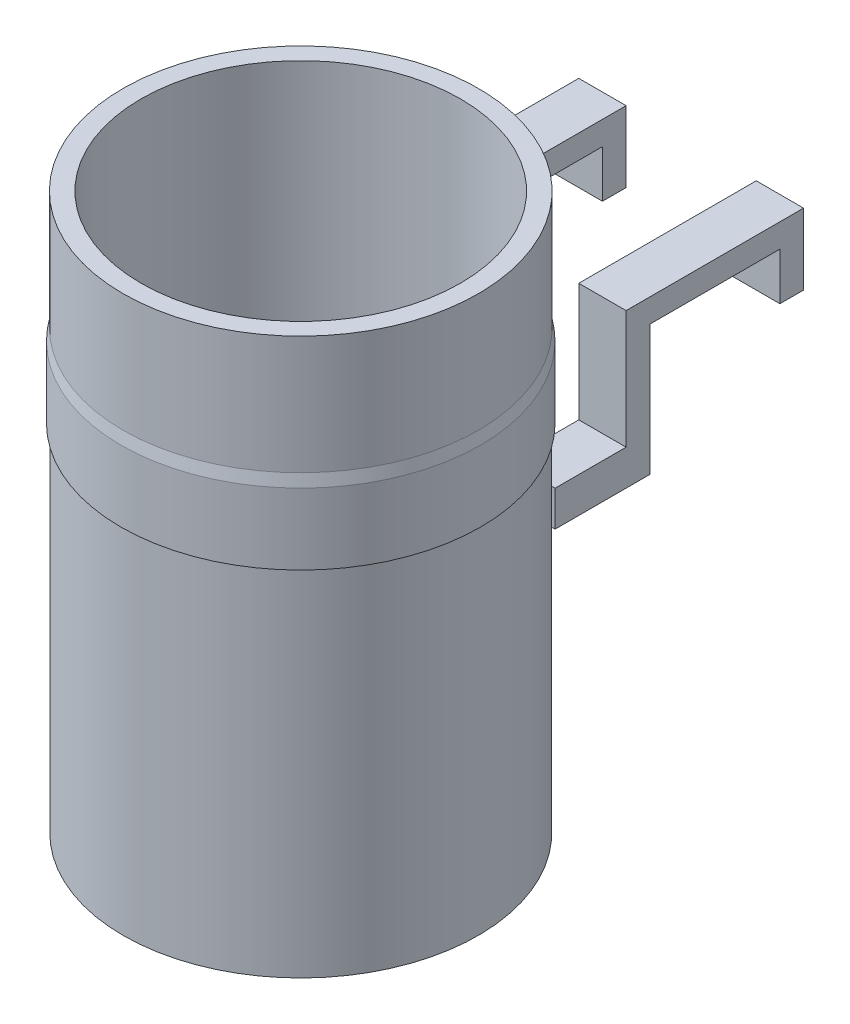
SolidWorks part; units mm, degrees
ref_plane "Front Plane" through (0, 0, 0) normal (0, 0, 1) x (1, 0, 0)
ref_plane "Top Plane" through (0, 0, 0) normal (0, 1, 0) x (1, 0, 0)
ref_plane "Right Plane" through (0, 0, 0) normal (1, 0, 0) x (0, 0, -1)
sketch "Sketch1" plane through (0, 0, 0) normal (0, 1, 0) x (1, 0, 0)
  circle A0 centre (-42.3748, 0) radius 75
  dimension "D1" = 150
extrude "Boss-Extrude1" add sketch "Sketch1" along normal blind 150
sketch "Sketch3" plane through (0, 150, 0) normal (0, 1, 0) x (1, 0, 0)
  circle A0 centre (-42.3748, 0) radius 76
  dimension "D1" = 152
extrude "Boss-Extrude3" add sketch "Sketch3" along normal blind 30
sketch "Sketch4" plane through (0, 180, 0) normal (0, 1, 0) x (1, 0, 0)
  circle A0 centre (-42.3748, 0) radius 76
extrude "Boss-Extrude4" add sketch "Sketch4" along normal blind 5 draft 10
sketch "Sketch5" plane through (0, 185, 0) normal (0, 1, 0) x (1, 0, 0)
  circle A0 centre (-42.3748, 0) radius 75.1184
extrude "Boss-Extrude5" add sketch "Sketch5" along normal blind 50
sketch "Sketch6" plane through (0, 235, 0) normal (0, 1, 0) x (1, 0, 0)
  circle A1 centre (-42.3748, 0) radius 67.5
  dimension "D1" = 135
ref_plane "Plane1" through (0, 0, -80) normal (0, 0, 1) x (1, 0, 0)
sketch "Sketch8" plane through (0, 0, -80) normal (0, 0, 1) x (1, 0, 0)
  line L0 (-117.3748, 150) -> (-117.3748, 0) construction
  line L1 (-14.8748, 120) -> (5.1252, 120)
  line L2 (-14.8748, 120) -> (-14.8748, 105)
  line L3 (-14.8748, 105) -> (5.1252, 105)
  line L4 (5.1252, 120) -> (5.1252, 105)
  line L5 (-89.8748, 120) -> (-69.8748, 120)
  line L6 (-89.8748, 120) -> (-89.8748, 105)
  line L7 (-89.8748, 105) -> (-69.8748, 105)
  line L8 (-69.8748, 120) -> (-69.8748, 105)
  line L9 (32.6252, 0) -> (32.6252, 150) construction
  line L10 (-117.3748, 150) -> (32.6252, 150) construction
  point P12 (-14.8748, 112.5)
  dimension "D1" = 27.5
  dimension "D2" = 27.5
  dimension "D3" = 20
  dimension "D4" = 20
  dimension "D5" = 55
  dimension "D6" = 15
  dimension "D7" = 15
  dimension "D8" = 30
  dimension "D9" = 30
extrude "Boss-Extrude6" add sketch "Sketch8" along normal blind 20 and the other way blind 20
sketch "Sketch9" plane through (0, 120, 0) normal (0, 1, 0) x (1, 0, 0)
  line L0 (-14.8748, 100) -> (-14.8748, 69.7764) construction
  line L1 (5.1252, 100) -> (-14.8748, 100)
  line L2 (5.1252, 100) -> (5.1252, 90)
  line L3 (5.1252, 90) -> (-14.8748, 90)
  line L4 (-14.8748, 100) -> (-14.8748, 90)
  dimension "D1" = 10
extrude "Boss-Extrude7" add sketch "Sketch9" along normal blind 50
sketch "Sketch10" plane through (0, 0, -100) normal (0, 0, -1) x (-1, 0, 0)
  line L0 (14.8748, 170) -> (14.8748, 105) construction
  line L1 (-5.1252, 170) -> (14.8748, 170)
  line L2 (-5.1252, 170) -> (-5.1252, 160)
  line L3 (-5.1252, 160) -> (14.8748, 160)
  line L4 (14.8748, 170) -> (14.8748, 160)
  dimension "D1" = 10
extrude "Boss-Extrude8" add sketch "Sketch10" along normal blind 65
sketch "Sketch11" plane through (0, 120, 0) normal (0, 1, 0) x (1, 0, 0)
  line L0 (-89.8748, 100) -> (-89.8748, 60) construction
  line L1 (-69.8748, 100) -> (-89.8748, 100)
  line L2 (-69.8748, 100) -> (-69.8748, 90)
  line L3 (-69.8748, 90) -> (-89.8748, 90)
  line L4 (-89.8748, 100) -> (-89.8748, 90)
  dimension "D1" = 10
extrude "Boss-Extrude9" add sketch "Sketch11" along normal blind 50
sketch "Sketch12" plane through (0, 0, -100) normal (0, 0, -1) x (-1, 0, 0)
  line L0 (89.8748, 170) -> (89.8748, 105) construction
  line L1 (69.8748, 170) -> (89.8748, 170)
  line L2 (69.8748, 170) -> (69.8748, 160)
  line L3 (69.8748, 160) -> (89.8748, 160)
  line L4 (89.8748, 170) -> (89.8748, 160)
  dimension "D1" = 10
extrude "Boss-Extrude10" add sketch "Sketch12" along normal blind 65
sketch "Sketch13" plane through (0, 160, 0) normal (0, -1, 0) x (1, 0, 0)
  line L0 (-14.8748, -165) -> (-14.8748, -100) construction
  line L1 (5.1252, -165) -> (-14.8748, -165)
  line L2 (5.1252, -165) -> (5.1252, -155)
  line L3 (5.1252, -155) -> (-14.8748, -155)
  line L4 (-14.8748, -165) -> (-14.8748, -155)
  line L5 (-89.8748, -165) -> (-89.8748, -100) construction
  line L6 (-69.8748, -165) -> (-89.8748, -165)
  line L7 (-69.8748, -165) -> (-69.8748, -155)
  line L8 (-69.8748, -155) -> (-89.8748, -155)
  line L9 (-89.8748, -165) -> (-89.8748, -155)
  dimension "D1" = 10
  dimension "D2" = 10
extrude "Boss-Extrude11" add sketch "Sketch13" along normal blind 20
extrude "Cut-Extrude2" cut sketch "Sketch6" against normal blind 200
